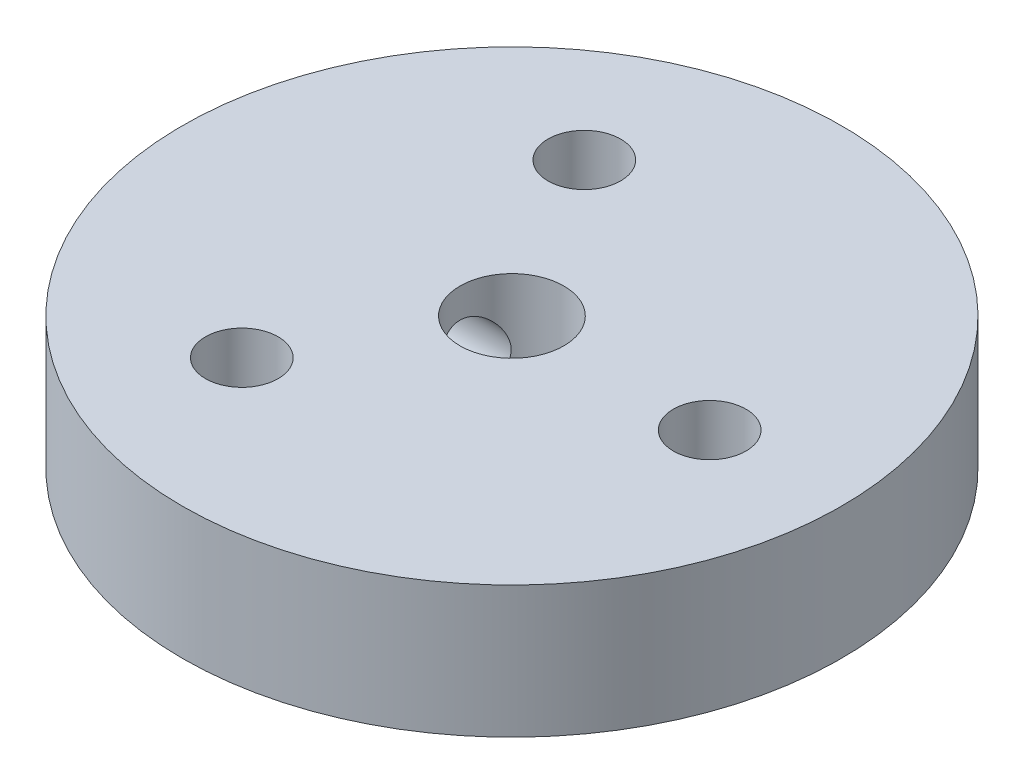
SolidWorks part; units mm, degrees
ref_plane "Front Plane" through (0, 0, 0) normal (0, 0, 1) x (1, 0, 0)
ref_plane "Top Plane" through (0, 0, 0) normal (0, 1, 0) x (1, 0, 0)
ref_plane "Right Plane" through (0, 0, 0) normal (1, 0, 0) x (0, 0, -1)
sketch "Sketch1" plane through (0, 0, 0) normal (0, 1, 0) x (1, 0, 0)
  circle A0 centre (0, 0) radius 2.5
  circle A1 centre (0, 0) radius 15.875
  circle A2 centre (9.525, 0) radius 1.75
  circle A3 centre (-4.7625, -8.2489) radius 1.75
  circle A4 centre (-4.7625, 8.2489) radius 1.75
  point P12 (0, 0)
  dimension "D1" = 5
  dimension "D2" = 31.75
  dimension "D5" = 3.5
  dimension "D3" = 9.525
  dimension "D4" = 3
extrude "Boss-Extrude2" add sketch "Sketch1" along normal mid plane 6.35
sketch "Sketch3" plane through (0, 0, 0) normal (1, 0, 0) x (0, 0, -1)
  circle A0 centre (0, 0) radius 1.75
  dimension "D1" = 3.5
extrude "Cut-Extrude1" cut sketch "Sketch3" against normal through all
equation "\"tightTol\" = 0.005in"
equation "\"normTol\"= 0.01in"
equation "\"looseTol\"= 0.02in"
equation "\"D1@Sketch1\"=5mm"
equation "\"D1@Sketch3\"=3.5mm"
equation "\"D5@Sketch1\"=3.5mm"
